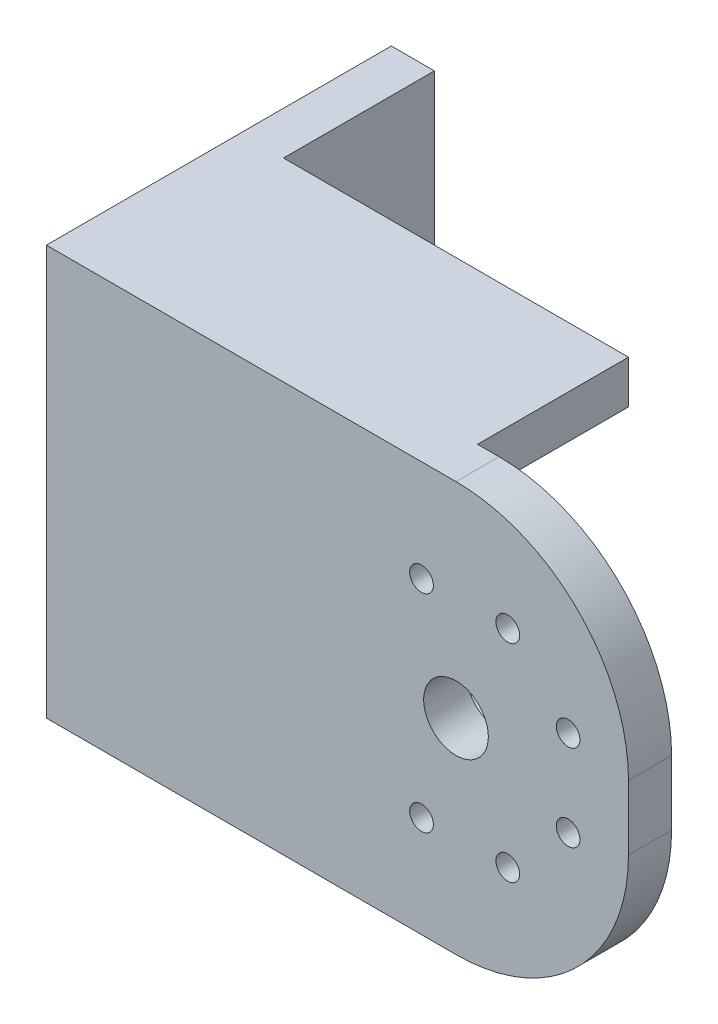
SolidWorks part; units mm, degrees
ref_plane "Front Plane" through (0, 0, 0) normal (0, 0, 1) x (1, 0, 0)
ref_plane "Top Plane" through (0, 0, 0) normal (0, 1, 0) x (1, 0, 0)
ref_plane "Right Plane" through (0, 0, 0) normal (1, 0, 0) x (0, 0, -1)
sketch "Sketch3" plane through (0, 0, 0) normal (0, 0, 1) x (1, 0, 0)
  line L6 (68.6171, 80.0599) -> (163.6171, 80.0599)
  line L10 (68.6171, 80.0599) -> (68.6171, -14.9401)
  line L36 (-101.4371, 49.8561) -> (-17.2351, 49.8561) construction
  line L70 (68.6171, -14.9401) -> (163.6171, -14.9401)
  line L71 (203.6171, 40.0599) -> (203.6171, 25.0599)
  circle A22 centre (163.6171, 32.5599) radius 7.5
  circle A23 centre (189.6171, 42.5599) radius 2.75
  circle A24 centre (155.6171, 56.5599) radius 2.75
  circle A25 centre (175.6171, 56.5599) radius 2.75
  circle A26 centre (155.6171, 8.5599) radius 2.75
  circle A27 centre (175.6171, 8.5599) radius 2.75
  circle A28 centre (189.6171, 22.5599) radius 2.75
  arc A29 (163.6171, -14.9401) -> (203.6171, 25.0599) centre (163.6171, 25.0599) ccw
  arc A30 (163.6171, 80.0599) -> (203.6171, 40.0599) centre (163.6171, 40.0599) cw
  point P23 (203.6171, 80.0599)
  dimension "D2" = 5.5
  dimension "D3" = 10
  dimension "D4" = 26
  dimension "D7" = 5.5
  dimension "D21" = 135
  dimension "D22" = 40
  dimension "D23" = 47.5
  dimension "D1" = 15
  dimension "D5" = 5.5
  dimension "D6" = 5.5
  dimension "D8" = 5.5
  dimension "D9" = 5.5
  dimension "D24" = 40
  dimension "D10" = 8
  dimension "D11" = 24
  dimension "D12" = 20
  dimension "D15" = 20
  dimension "D16" = 8
  dimension "D17" = 20
  dimension "D18" = 48
  dimension "D19" = 48
  dimension "D20" = 95
  dimension "D13" = 26
  dimension "D14" = 24
extrude "Boss-Extrude1" add sketch "Sketch3" along normal blind 10
sketch "Sketch4" plane through (0, 0, 0) normal (0, 0, -1) x (-1, 0, 0)
  line L0 (-68.6171, -14.9401) -> (-163.6171, -14.9401) construction
  line L1 (-68.6171, 80.0599) -> (-78.6171, 80.0599)
  line L2 (-68.6171, 80.0599) -> (-68.6171, -14.9401)
  line L3 (-68.6171, -14.9401) -> (-78.6171, -14.9401)
  line L4 (-78.6171, 80.0599) -> (-78.6171, -14.9401)
  dimension "D1" = 10
extrude "Boss-Extrude2" add sketch "Sketch4" along normal blind 70
sketch "Sketch5" plane through (0, 0, 0) normal (0, 0, -1) x (-1, 0, 0)
  line L1 (-78.6171, 80.0599) -> (-158.6171, 80.0599)
  line L2 (-78.6171, 80.0599) -> (-78.6171, 70.0599)
  line L3 (-78.6171, 70.0599) -> (-158.6171, 70.0599)
  line L4 (-158.6171, 80.0599) -> (-158.6171, 70.0599)
  line L5 (-78.6171, -14.9401) -> (-158.6171, -14.9401)
  line L6 (-78.6171, -14.9401) -> (-78.6171, -4.9401)
  line L7 (-78.6171, -4.9401) -> (-158.6171, -4.9401)
  line L8 (-158.6171, -14.9401) -> (-158.6171, -4.9401)
  dimension "D1" = 10
  dimension "D2" = 10
  dimension "D3" = 80
  dimension "D4" = 80
extrude "Boss-Extrude3" add sketch "Sketch5" along normal blind 35
sketch "Sketch6" plane through (0, -14.9401, 0) normal (0, -1, 0) x (1, 0, 0)
  line L0 (52.25, 0) -> (-52.25, 0) construction
  line L1 (88.6171, 0) -> (120.6171, 0)
  line L2 (88.6171, 0) -> (88.6171, -36)
  line L3 (88.6171, -36) -> (120.6171, -36)
  line L4 (120.6171, 0) -> (120.6171, -36)
  line L5 (68.6171, 10) -> (68.6171, -70) construction
  dimension "D1" = 20
  dimension "D2" = 36
  dimension "D3" = 32
extrude "Cut-Extrude1" [suppressed] cut sketch "Sketch6" against normal blind 43.8
fillet "Fillet2" [suppressed] radius 15
sketch "Sketch8" plane through (68.6171, 0, 0) normal (-1, 0, 0) x (0, 0, 1)
  line L0 (10, 80.0599) -> (-70, 80.0599) construction
  line L1 (-40, 32.5599) -> (-56.1679, 25.863) construction
  line L2 (-70, 32.5599) -> (0, 32.5599) construction
  line L3 (-70, -14.9401) -> (-70, 80.0599) construction
  circle A0 centre (-40, 32.5599) radius 7.5
  circle A1 centre (-56.1679, 25.863) radius 2.75
  circle A2 centre (-56.1679, 39.2569) radius 2.75
  circle A3 centre (-46.697, 48.7278) radius 2.75
  circle A4 centre (-33.303, 48.7278) radius 2.75
  circle A5 centre (-23.8321, 39.2569) radius 2.75
  circle A6 centre (-23.8321, 25.863) radius 2.75
  circle A7 centre (-33.303, 16.392) radius 2.75
  circle A8 centre (-46.697, 16.392) radius 2.75
  point P27 (-40, 32.5599)
  dimension "D1" = 15
  dimension "D6" = 5.5
  dimension "D2" = 47.5
  dimension "D3" = 30
  dimension "D4" = 17.5
  dimension "D5" = 22.5
  dimension "D7" = 8
extrude "Cut-Extrude2" cut sketch "Sketch8" against normal blind 43.8
fillet "Fillet3" [suppressed] radius 3
